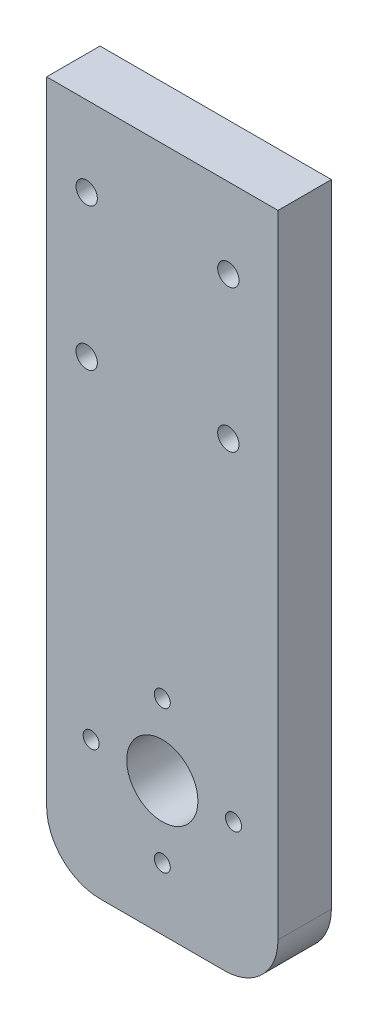
SolidWorks part; units mm, degrees
ref_plane "Plan de face" through (0, 0, 0) normal (0, 0, 1) x (1, 0, 0)
ref_plane "Plan de dessus" through (0, 0, 0) normal (0, 1, 0) x (1, 0, 0)
ref_plane "Plan de droite" through (0, 0, 0) normal (1, 0, 0) x (0, 0, -1)
sketch "Esquisse1" plane through (0, 0, 0) normal (0, 0, 1) x (1, 0, 0)
  line L0 (24.9164, -77.5735) -> (24.9164, -6.5735)
  line L1 (50.9164, -6.5735) -> (24.9164, -6.5735)
  line L2 (37.9164, 189.4329) -> (37.9164, -108.4772) construction
  line L3 (30.9164, -83.5735) -> (44.9164, -83.5735)
  line L11 (50.9164, -77.5735) -> (50.9164, -6.5735)
  arc A0 (44.9164, -83.5735) -> (50.9164, -77.5735) centre (44.9164, -77.5735) ccw
  arc A1 (24.9164, -77.5735) -> (30.9164, -83.5735) centre (30.9164, -77.5735) ccw
  circle A2 centre (29.9164, -68.5735) radius 0.9
  circle A3 centre (37.9164, -60.5735) radius 0.9
  circle A4 centre (45.9164, -68.5735) radius 0.9
  circle A5 centre (37.9164, -76.5735) radius 0.9
  circle A7 centre (37.9164, -68.5735) radius 4
  point P6 (50.9164, -83.5735)
  dimension "D3" = 6
  dimension "D6" = 1.8
  dimension "D7" = 1.8
  dimension "D8" = 1.8
  dimension "D9" = 1.8
  dimension "D4" = 8
  dimension "D1" = 77
  dimension "D5" = 15
extrude "Boss.-Extru.1" add sketch "Esquisse1" along normal blind 6
sketch "Esquisse2" plane through (0, 0, 0) normal (0, 0, -1) x (-1, 0, 0)
  line L2 (-24.9164, -6.5735) -> (-24.9164, -77.5735) construction
  line L3 (-50.9164, -6.5735) -> (-24.9164, -6.5735) construction
  line L5 (-50.9164, -77.5735) -> (-50.9164, -6.5735) construction
  circle A0 centre (-45.3364, -15.5735) radius 1.2
  circle A1 centre (-29.4164, -15.5735) radius 1.2
  circle A2 centre (-45.3364, -31.5735) radius 1.2
  circle A3 centre (-29.4164, -31.5735) radius 1.2
  dimension "D1" = 2.4
  dimension "D2" = 2.4
  dimension "D3" = 2.4
  dimension "D4" = 2.4
  dimension "D5" = 4.5
  dimension "D6" = 4.5
  dimension "D7" = 9
  dimension "D8" = 9
  dimension "D9" = 16
  dimension "D10" = 16
  dimension "D11" = 5.58
  dimension "D12" = 5.58
extrude "Enlèv. mat.-Extru.1" cut sketch "Esquisse2" against normal blind 10
